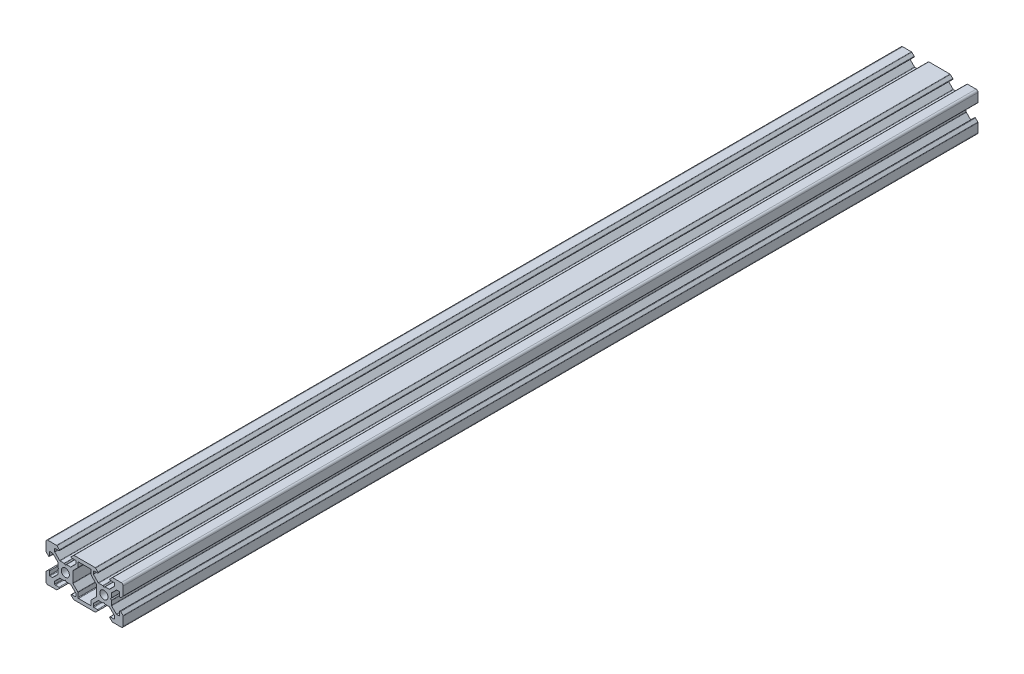
SolidWorks part; units mm, degrees
material "АД31Т ГОСТ 4784-97"
ref_plane "Спереди" through (0, 0, 0) normal (0, 0, 1) x (1, 0, 0)
ref_plane "Сверху" through (0, 0, 0) normal (0, 1, 0) x (1, 0, 0)
ref_plane "Справа" through (0, 0, 0) normal (1, 0, 0) x (0, 0, -1)
sketch "Эскиз1" plane through (0, 0, 0) normal (0, 0, 1) x (1, 0, 0)
  line L0 (12.9654, 0) -> (-12.9654, 0) construction
  line L1 (0, -12.9654) -> (0, 12.9654) construction
  line L2 (0, 0) -> (-18.3359, -18.3359) construction
  line L3 (-10, -10) -> (-10, -4.4)
  line L4 (-10, -4.4) -> (-8.2, -2.6)
  line L5 (-8.2, -2.6) -> (-8.2, -5.4993)
  line L6 (-8.2, -5.4993) -> (-6.56, -5.4993)
  line L7 (-6.56, -5.4993) -> (-3.9007, -2.84)
  line L8 (-3.9007, -2.84) -> (-3.9007, -0.5)
  line L9 (-3.9007, -0.5) -> (-3.4007, 0)
  line L10 (-0.5, -3.9007) -> (0, -3.4007)
  line L11 (-2.84, -3.9007) -> (-0.5, -3.9007)
  line L12 (-5.4993, -6.56) -> (-2.84, -3.9007)
  line L13 (-5.4993, -8.2) -> (-5.4993, -6.56)
  line L14 (-2.6, -8.2) -> (-5.4993, -8.2)
  line L15 (-4.4, -10) -> (-2.6, -8.2)
  line L16 (-10, -10) -> (-4.4, -10)
  line L17 (-10, 10) -> (-4.4, 10)
  line L18 (-4.4, 10) -> (-2.6, 8.2)
  line L19 (-2.6, 8.2) -> (-5.4993, 8.2)
  line L20 (-5.4993, 8.2) -> (-5.4993, 6.56)
  line L21 (-5.4993, 6.56) -> (-2.84, 3.9007)
  line L22 (-2.84, 3.9007) -> (-0.5, 3.9007)
  line L23 (-0.5, 3.9007) -> (0, 3.4007)
  line L24 (-3.9007, 0.5) -> (-3.4007, 0)
  line L25 (-3.9007, 2.84) -> (-3.9007, 0.5)
  line L26 (-6.56, 5.4993) -> (-3.9007, 2.84)
  line L27 (-8.2, 5.4993) -> (-6.56, 5.4993)
  line L28 (-8.2, 2.6) -> (-8.2, 5.4993)
  line L29 (-10, 4.4) -> (-8.2, 2.6)
  line L30 (-10, 10) -> (-10, 4.4)
  line L31 (0.5, 3.9007) -> (0, 3.4007)
  line L32 (0.5, -3.9007) -> (0, -3.4007)
  line L33 (10, -10) -> (10, 10) construction
  line L34 (3.9007, -0.5) -> (3.9007, 0.5)
  line L35 (6.56, -5.4993) -> (6.56, -8.2)
  line L36 (13.44, -5.4993) -> (16.0993, -2.84)
  line L37 (6.56, 5.4993) -> (3.9007, 2.84)
  line L38 (3.9007, 2.84) -> (3.9007, 0.5)
  line L39 (6.56, -8.2) -> (13.44, -8.2)
  line L40 (2.84, 3.9007) -> (0.5, 3.9007)
  line L41 (5.4993, 6.56) -> (2.84, 3.9007)
  line L42 (5.4993, 8.2) -> (5.4993, 6.56)
  line L43 (2.6, 8.2) -> (5.4993, 8.2)
  line L44 (4.4, 10) -> (2.6, 8.2)
  line L45 (15.6, 10) -> (4.4, 10)
  line L46 (15.6, -10) -> (4.4, -10)
  line L47 (4.4, -10) -> (2.6, -8.2)
  line L48 (2.6, -8.2) -> (5.4993, -8.2)
  line L49 (5.4993, -8.2) -> (5.4993, -6.56)
  line L50 (5.4993, -6.56) -> (2.84, -3.9007)
  line L51 (2.84, -3.9007) -> (0.5, -3.9007)
  line L52 (6.56, 5.4993) -> (6.56, 8.2)
  line L53 (3.9007, -2.84) -> (3.9007, -0.5)
  line L54 (6.56, -5.4993) -> (3.9007, -2.84)
  line L55 (16.0993, -2.84) -> (16.0993, -0.5)
  line L56 (6.56, 8.2) -> (13.44, 8.2)
  line L57 (13.44, 5.4993) -> (13.44, 8.2)
  line L58 (17.16, -3.9007) -> (19.5, -3.9007)
  line L59 (14.5007, -6.56) -> (17.16, -3.9007)
  line L60 (14.5007, -8.2) -> (14.5007, -6.56)
  line L61 (17.4, -8.2) -> (14.5007, -8.2)
  line L62 (15.6, -10) -> (17.4, -8.2)
  line L63 (15.6, 10) -> (17.4, 8.2)
  line L64 (17.4, 8.2) -> (14.5007, 8.2)
  line L65 (14.5007, 8.2) -> (14.5007, 6.56)
  line L66 (14.5007, 6.56) -> (17.16, 3.9007)
  line L67 (17.16, 3.9007) -> (19.5, 3.9007)
  line L68 (16.0993, 2.84) -> (16.0993, 0.5)
  line L69 (13.44, 5.4993) -> (16.0993, 2.84)
  line L70 (13.44, -5.4993) -> (13.44, -8.2)
  line L71 (16.0993, -0.5) -> (16.0993, 0.5)
  line L72 (19.5, -3.9007) -> (20, -3.4007)
  line L73 (19.5, 3.9007) -> (20, 3.4007)
  line L74 (30, 10) -> (30, 4.4)
  line L75 (30, 4.4) -> (28.2, 2.6)
  line L76 (28.2, 2.6) -> (28.2, 5.4993)
  line L77 (28.2, 5.4993) -> (26.56, 5.4993)
  line L78 (26.56, 5.4993) -> (23.9007, 2.84)
  line L79 (23.9007, 2.84) -> (23.9007, 0.5)
  line L80 (23.9007, 0.5) -> (23.4007, 0)
  line L81 (20.5, 3.9007) -> (20, 3.4007)
  line L82 (22.84, 3.9007) -> (20.5, 3.9007)
  line L83 (25.4993, 6.56) -> (22.84, 3.9007)
  line L84 (25.4993, 8.2) -> (25.4993, 6.56)
  line L85 (22.6, 8.2) -> (25.4993, 8.2)
  line L86 (24.4, 10) -> (22.6, 8.2)
  line L87 (30, 10) -> (24.4, 10)
  line L88 (30, -10) -> (24.4, -10)
  line L89 (24.4, -10) -> (22.6, -8.2)
  line L90 (22.6, -8.2) -> (25.4993, -8.2)
  line L91 (25.4993, -8.2) -> (25.4993, -6.56)
  line L92 (25.4993, -6.56) -> (22.84, -3.9007)
  line L93 (22.84, -3.9007) -> (20.5, -3.9007)
  line L94 (20.5, -3.9007) -> (20, -3.4007)
  line L95 (23.9007, -0.5) -> (23.4007, 0)
  line L96 (23.9007, -2.84) -> (23.9007, -0.5)
  line L97 (26.56, -5.4993) -> (23.9007, -2.84)
  line L98 (28.2, -5.4993) -> (26.56, -5.4993)
  line L99 (28.2, -2.6) -> (28.2, -5.4993)
  line L100 (30, -4.4) -> (28.2, -2.6)
  line L101 (30, -10) -> (30, -4.4)
  circle A0 centre (0, 0) radius 2.1
  circle A1 centre (20, 0) radius 2.1
  point P62 (10, 8.2)
  point P80 (10, -8.2)
  dimension "D5" = 2.6
  dimension "D10" = 4.2
  dimension "D2" = 10
  dimension "D3" = 1.64
  dimension "D4" = 1.5
  dimension "D6" = 1.8
  dimension "D7" = 2.84
  dimension "D8" = 0.5
  dimension "D9" = 45
extrude "Бобышка-Вытянуть1" add sketch "Эскиз1" along normal blind 443
fillet "Скругление1" radius 1 4 edges at (-10, 10, 221.5) (-10, -10, 221.5) (30, 10, 221.5) (30, -10, 221.5)
fillet "Скругление2" radius 0.3 83 edges at (-4.4, 10, 221.5) (-2.6, 8.2, 221.5) (-5.4993, 8.2, 221.5) (-5.4993, 6.56, 221.5) (-2.84, 3.9007, 221.5) (-0.5, 3.9007, 221.5) (0.5, 3.9007, 221.5) (2.84, 3.9007, 221.5) (5.4993, 6.56, 221.5) (4.4, 10, 221.5) (5.4993, 8.2, 221.5) (2.6, 8.2, 221.5) (3.9007, 2.84, 221.5) (3.9007, -2.84, 221.5) (4.4, -10, 221.5) (2.6, -8.2, 221.5) (5.4993, -8.2, 221.5) (5.4993, -6.56, 221.5) (2.84, -3.9007, 221.5) (0.5, -3.9007, 221.5) (-0.5, -3.9007, 221.5) (-2.84, -3.9007, 221.5) (-5.4993, -6.56, 221.5) (-5.4993, -8.2, 221.5) (-2.6, -8.2, 221.5) (-10, -4.4, 221.5) (-8.2, -2.6, 221.5) (-8.2, -5.4993, 221.5) (-6.56, -5.4993, 221.5) (-3.9007, -2.84, 221.5) (-3.9007, -0.5, 221.5) (-3.9007, 0.5, 221.5) (-3.9007, 2.84, 221.5) (-6.56, 5.4993, 221.5) (-8.2, 5.4993, 221.5) (-8.2, 2.6, 221.5) (-10, 4.4, 221.5) (6.56, -5.4993, 221.5) (6.56, 5.4993, 221.5) (6.56, 8.2, 221.5) (13.44, 8.2, 221.5) (13.44, 5.4993, 221.5) (16.0993, 2.84, 221.5) (16.0993, -2.84, 221.5) (13.44, -5.4993, 221.5) (13.44, -8.2, 221.5) (6.56, -8.2, 221.5) (15.6, 10, 221.5) (17.4, 8.2, 221.5) (14.5007, 8.2, 221.5) (14.5007, 6.56, 221.5) (17.16, 3.9007, 221.5) (19.5, 3.9007, 221.5) (20.5, 3.9007, 221.5) (22.84, 3.9007, 221.5) (25.4993, 6.56, 221.5) (25.4993, 8.2, 221.5) (22.6, 8.2, 221.5) (24.4, 10, 221.5) (30, 4.4, 221.5) (28.2, 2.6, 221.5) (28.2, 5.4993, 221.5) (26.56, 5.4993, 221.5) (23.9007, 2.84, 221.5) (23.9007, 0.5, 221.5) (23.9007, -0.5, 221.5) (23.9007, -2.84, 221.5) (26.56, -5.4993, 221.5) (28.2, -5.4993, 221.5) (28.2, -2.6, 221.5) (30, -4.4, 221.5) (24.4, -10, 221.5) (22.6, -8.2, 221.5) (25.4993, -8.2, 221.5) (25.4993, -6.56, 221.5) (22.84, -3.9007, 221.5) (20.5, -3.9007, 221.5) (19.5, -3.9007, 221.5) (17.16, -3.9007, 221.5) (14.5007, -6.56, 221.5) (14.5007, -8.2, 221.5) (17.4, -8.2, 221.5) (15.6, -10, 221.5)
